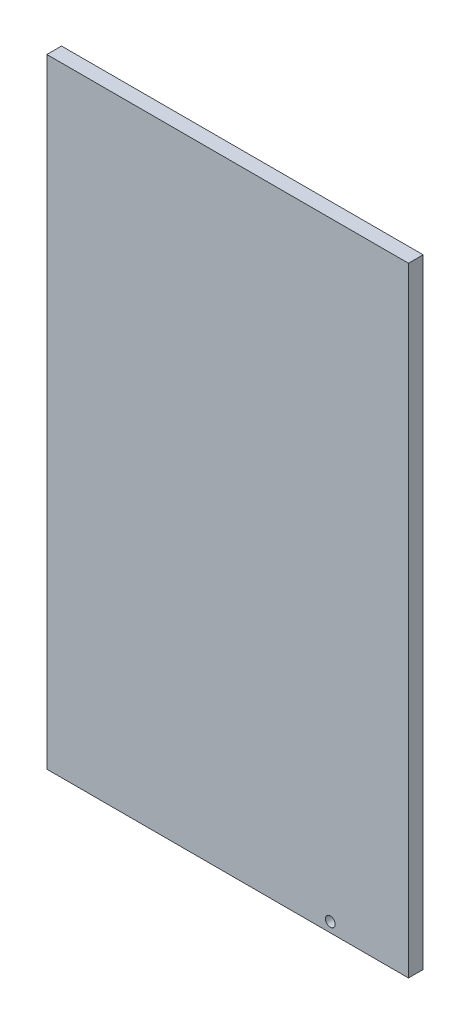
SolidWorks part; units mm, degrees
material "Perspex (TM) GS Acrylic Cast Sheet"
ref_plane "Front Plane" through (0, 0, 0) normal (0, 0, 1) x (1, 0, 0)
ref_plane "Top Plane" through (0, 0, 0) normal (0, 1, 0) x (1, 0, 0)
ref_plane "Right Plane" through (0, 0, 0) normal (1, 0, 0) x (0, 0, -1)
sketch "Sketch1" plane through (0, 0, 0) normal (0, 0, 1) x (1, 0, 0)
  line L1 (-111, -190) -> (111, -190)
  line L2 (-111, -190) -> (-111, 190)
  line L3 (-111, 190) -> (111, 190)
  line L4 (111, -190) -> (111, 190)
  line L5 (-111, -190) -> (111, 190) construction
  line L6 (-111, 190) -> (111, -190) construction
  point P0 (0, 0)
  dimension "D1" = 222
  dimension "D2" = 380
extrude "Boss-Extrude1" add sketch "Sketch1" along normal blind 9
sketch "Sketch2" plane through (0, 0, 9) normal (0, 0, 1) x (1, 0, 0)
  line L0 (111, -190) -> (111, 190) construction
  line L1 (-111, -190) -> (111, -190) construction
  circle A0 centre (63, -184) radius 3
  dimension "D1" = 6
  dimension "D2" = 48
  dimension "D3" = 6
extrude "Cut-Extrude1" cut sketch "Sketch2" against normal through all
sketch "Sketch4" [suppressed] plane through (0, 0, 0) normal (0, 0, -1) x (-1, 0, 0)
  circle A0 centre (-30, -170) radius 5.5
  circle A1 centre (-90, -170) radius 5.5
  circle A2 centre (30, -170) radius 5.5
  circle A3 centre (90, -170) radius 5.5
  dimension "D1" = 11
extrude "Cut-Extrude2" [suppressed] cut sketch "Sketch4" against normal through all
equation "\"PCLength\"= 145mm'Length across I/O from PS to GPU"
equation "\"PCWidth\"= 340mm'Distance of longest part parallel to GPU(ussually GPU)"
equation "\"PCHeight\"= 180mm'Tallest point with mobo laying flat"
equation "\"WallThickness\"= 9mm'Thickness of each outer tank wall"
equation "\"ThermoBarrierThickness\"= 6mm'Thickness of barrier between hot side and cold side"
equation "\"HotSideGap\"= 36mm'Space in the hot side for a pump"
equation "\"PCClearance\"= 40mm'Clearance from top of tank to top of PC"
equation "\"RadiatorHeight\"= 275mm'Final Height from ground of radiators"
equation "\"D1@Sketch1\"=\"PCHeight\" + \"ThermoBarrierThickness\" + \"HotSideGap\""
equation "\"D2@Sketch1\"=\"PCWidth\" + \"PCClearance\""
equation "\"D1@Boss-Extrude1\"=\"WallThickness\""
equation "\"D2@Sketch2\"=\"HotSideGap\" + \"ThermoBarrierThickness\" + 6"
